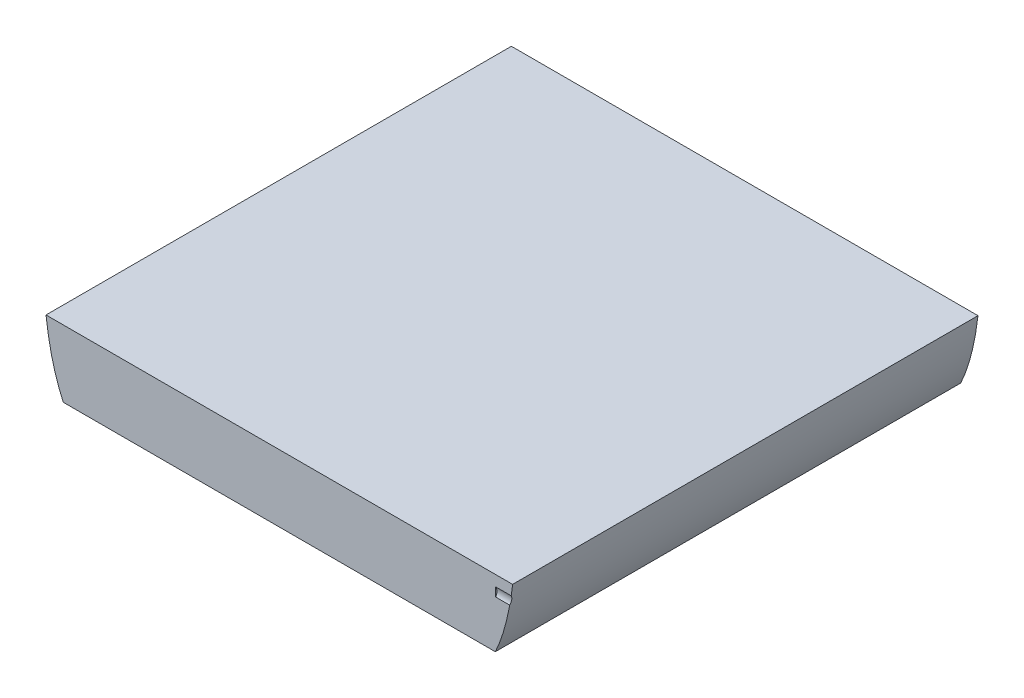
SolidWorks part; units mm, degrees
ref_plane "Front Plane" through (0, 0, 0) normal (0, 0, 1) x (1, 0, 0)
ref_plane "Top Plane" through (0, 0, 0) normal (0, 1, 0) x (1, 0, 0)
ref_plane "Right Plane" through (0, 0, 0) normal (1, 0, 0) x (0, 0, -1)
sketch "Sketch1" plane through (0, 0, 0) normal (0, 0, 1) x (1, 0, 0)
  line L0 (0, 0) -> (0, 222.758) construction
  line L2 (-350.1769, 222.758) -> (0, 222.758)
  line L3 (0, 222.758) -> (350.1769, 222.758)
  conic Q0 (350.1769, 222.758) -> (0, 0) control (323.6021, 0) rho 0.570465
  conic Q1 (-350.1769, 222.758) -> (0, 0) control (-323.6021, 0) rho 0.570465
extrude "Boss-Extrude1" add sketch "Sketch1" against normal blind 349.25 and the other way blind 349.25 contours Q0 Q1 L2 L3
sketch "Sketch6" plane through (0, 0, 0) normal (1, 0, 0) x (0, 0, -1)
  line L0 (0, 0) -> (402.7895, 12.7)
  line L1 (0, 0) -> (0, 317.8845) construction
  line L2 (0, 0) -> (-402.7895, 12.7)
  dimension "D1" = 12.7
ref_plane "Plane1" through (304.8, 0, 0) normal (1, 0, 0) x (0, 0, -1)
ref_plane "Plane2" [suppressed] through (0, 0, 401.32) normal (0, 0, 1) x (1, 0, 0)
sketch "Sketch29" plane through (0, 0, 0) normal (1, 0, 0) x (0, 0, -1)
  line L0 (0, 7.9367) -> (74.9675, 7.9367)
  line L1 (74.9675, 7.9367) -> (308.7791, 142.4931)
  line L3 (308.7791, 142.4931) -> (642.4614, 142.4931)
  point P6 (0, -63.5)
sweep "Engine Line" [suppressed] add path "Sketch29" circular profile diameter 12.7 parameters "D3"=12.7
sketch "Sketch42" plane through (0, 0, 0) normal (0, 0, 1) x (1, 0, 0)
  circle A0 centre (0, 6.35) radius 6.35
extrude "Boss-Extrude2" [suppressed] add sketch "Sketch42" against normal blind 635
sketch "Sketch43" plane through (0, 0, -349.25) normal (0, 0, -1) x (-1, 0, 0)
  circle A0 centre (0, 209.4482) radius 6.35
extrude "Boss-Extrude3" [suppressed] add sketch "Sketch43" along normal blind 142.748
ref_plane "Plane4" through (0, 0, 381) normal (0, 0, 1) x (1, 0, 0)
sketch "Sketch41" plane through (0, 0, 381) normal (0, 0, 1) x (1, 0, 0)
  line L0 (-0.3885, -71.0751) -> (-0.3885, 316.4102) construction
  conic Q0 (-0.3885, -71.0751) -> (301.9685, 246.7379) control (301.9685, -71.1416) rho 0.504796
  conic Q1 (-0.3885, -71.0751) -> (-302.7456, 246.7379) control (-302.7456, -71.1416) rho 0.504796
ref_plane "Plane5" through (350.1769, 0, 0) normal (1, 0, 0) x (0, 0, -1)
sketch "Sketch44" plane through (350.1769, 0, 0) normal (1, 0, 0) x (0, 0, -1)
  circle A0 centre (-360.0842, 200.1725) radius 12.7
extrude "Cut-Extrude1" cut sketch "Sketch44" against normal blind 25.4
sketch "Sketch45" plane through (0, 0, 0) normal (0, 0, 1) x (1, 0, 0)
  line L0 (-363.6888, 122.174) -> (403.1456, 122.174)
  line L1 (-350.1769, 222.758) -> (350.1769, 222.758) construction
  dimension "D1" = 100.584
split "Split1" trim tools "Sketch45" bodies to split 125 resulting bodies 127
